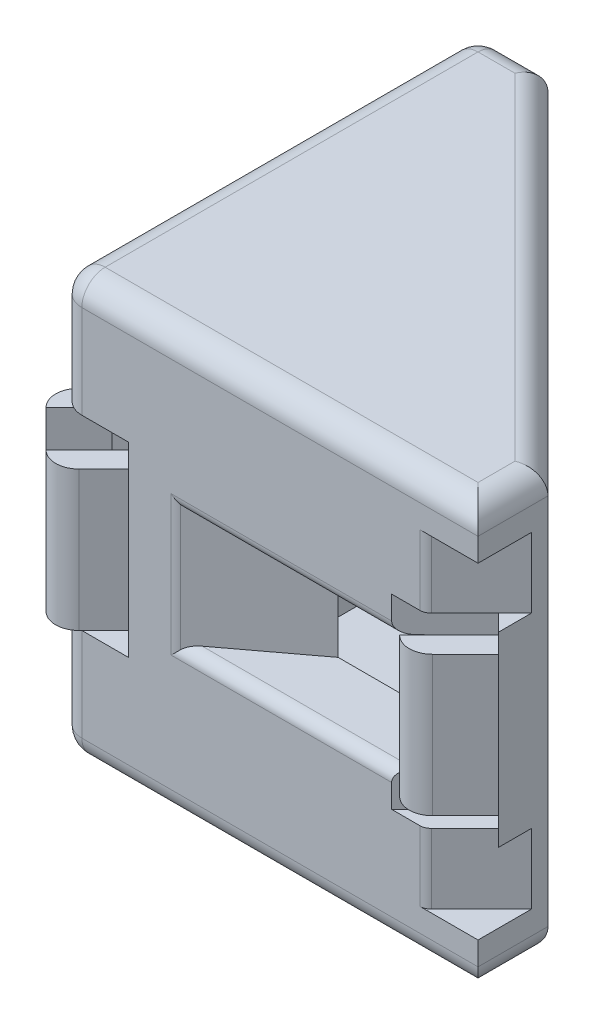
SolidWorks part; units mm, degrees
material "AISI Type A2 Tool Steel"
ref_plane "Front Plane" through (0, 0, 0) normal (0, 0, 1) x (1, 0, 0)
ref_plane "Top Plane" through (0, 0, 0) normal (0, 1, 0) x (1, 0, 0)
ref_plane "Right Plane" through (0, 0, 0) normal (1, 0, 0) x (0, 0, -1)
sketch "Sketch1" plane through (0, 0, 0) normal (0, 1, 0) x (1, 0, 0)
  line L0 (0, 0) -> (0, 18)
  line L1 (0, 18) -> (3, 18)
  line L2 (3, 18) -> (18, 3)
  line L3 (18, 3) -> (18, 0)
  line L4 (18, 0) -> (0, 0)
  dimension "D1" = 18
  dimension "D2" = 18
  dimension "D3" = 3
  dimension "D4" = 3
extrude "Boss-Extrude1" add sketch "Sketch1" along normal blind 18
sketch "Sketch2" plane through (0, 0, -18) normal (0, 0, -1) x (-1, 0, 0)
  line L0 (-18, 18) -> (-18, 0) construction
  line L1 (-18, 16) -> (-3, 16)
  line L2 (-18, 16) -> (-18, 2)
  line L3 (-18, 2) -> (-3, 2)
  line L4 (-3, 16) -> (-3, 2)
  line L5 (-3, 18) -> (-3, 0) construction
  line L6 (-18, 18) -> (-3, 18) construction
  line L7 (-18, 0) -> (-3, 0) construction
  dimension "D1" = 2
  dimension "D2" = 2
extrude "Cut-Extrude1" cut sketch "Sketch2" against normal up to vertex (15 mm away) up to point (18, 18, -3)
sketch "Sketch3" plane through (0, 0, -3) normal (0, 0, -1) x (-1, 0, 0)
  line L0 (-18, 16) -> (-18, 2) construction
  line L1 (-15, 11.5) -> (-9, 11.5)
  line L2 (-15, 11.5) -> (-15, 6.5)
  line L3 (-15, 6.5) -> (-9, 6.5)
  line L4 (-9, 11.5) -> (-9, 6.5)
  point P4 (-18, 9)
  point P7 (-15, 9)
  dimension "D1" = 6
  dimension "D2" = 5
  dimension "D3" = 3
sketch "Sketch4" plane through (3, 0, 0) normal (1, 0, 0) x (0, 0, -1)
  line L0 (9, 11.5) -> (15, 11.5)
  line L1 (9, 11.5) -> (9, 6.5)
  line L2 (9, 6.5) -> (15, 6.5)
  line L3 (15, 11.5) -> (15, 6.5)
  line L4 (18, 2) -> (18, 16) construction
  point P7 (18, 9)
  point P8 (15, 9)
  dimension "D1" = 3
  dimension "D2" = 6
  dimension "D3" = 5
sketch "Sketch5" plane through (0, 0, 0) normal (-1, 0, 0) x (0, 0, 1)
  line L1 (-15, 11.5) -> (-5, 11.5)
  line L2 (-15, 11.5) -> (-15, 6.5)
  line L3 (-15, 6.5) -> (-5, 6.5)
  line L4 (-5, 11.5) -> (-5, 6.5)
  dimension "D1" = 10
  dimension "D2" = 5
sketch "Sketch6" plane through (0, 0, 0) normal (0, 0, 1) x (1, 0, 0)
  line L1 (15, 11.5) -> (5, 11.5)
  line L2 (15, 11.5) -> (15, 6.5)
  line L3 (15, 6.5) -> (5, 6.5)
  line L4 (5, 11.5) -> (5, 6.5)
  dimension "D1" = 10
  dimension "D2" = 5
loft "Cut-Loft1" cut profiles "Sketch3", "Sketch6" connector at (9, 11.5, -3) connector at (5, 11.5, 0)
loft "Cut-Loft2" cut profiles "Sketch4", "Sketch5" connector at (3, 6.5, -9) connector at (0, 6.5, -5)
sketch "Sketch7" plane through (10.5, 0, -10.5) normal (0.7071, 0, -0.7071) x (-0.7071, 0, -0.7071)
  line L0 (10.6066, 2) -> (10.6066, 16) construction
  line L1 (11.1066, 16) -> (13.1066, 16)
  line L2 (11.1066, 16) -> (11.1066, 13)
  line L3 (11.1066, 13) -> (13.1066, 13)
  line L4 (13.1066, 16) -> (13.1066, 13)
  line L5 (11.1066, 5) -> (13.1066, 5)
  line L6 (11.1066, 5) -> (11.1066, 2)
  line L7 (11.1066, 2) -> (13.1066, 2)
  line L8 (13.1066, 5) -> (13.1066, 2)
  line L9 (-10.6066, 16) -> (10.6066, 16) construction
  line L10 (-13.1066, 16) -> (-11.1066, 16)
  line L11 (-13.1066, 16) -> (-13.1066, 13)
  line L12 (-13.1066, 13) -> (-11.1066, 13)
  line L13 (-11.1066, 16) -> (-11.1066, 13)
  line L14 (-13.1066, 5) -> (-11.1066, 5)
  line L15 (-13.1066, 5) -> (-13.1066, 2)
  line L16 (-13.1066, 2) -> (-11.1066, 2)
  line L17 (-11.1066, 5) -> (-11.1066, 2)
  line L18 (-10.6066, 16) -> (-10.6066, 2) construction
  line L19 (0, 16) -> (-10.6066, 16) construction
  point P10 (12.1066, 13)
  dimension "D1" = 2
  dimension "D2" = 2
  dimension "D3" = 0.5
  dimension "D4" = 0.5
  dimension "D5" = 3
  dimension "D6" = 3
  dimension "D7" = 8
  dimension "D8" = 8
  dimension "D9" = 2
  dimension "D10" = 3
  dimension "D11" = 0.5
extrude "Cut-Extrude2" cut sketch "Sketch7" against normal up to surface (1.7426 mm away) up to face at (0, 9, -9)
sketch "Sketch8" plane through (0, 5, 0) normal (0, -1, 0) x (1, 0, 0)
  line L5 (0.7072, -18) -> (2.2071, -16.5)
  line L6 (2.2929, -18) -> (0, -18) construction
  line L7 (0, -15.7071) -> (2.2929, -18) construction
  line L8 (2.2071, -16.5) -> (-0.114, -14.1789)
  line L9 (-0.114, -14.1789) -> (-1.614, -15.6789)
  line L10 (-1.614, -15.6789) -> (0.7072, -18)
  dimension "D1" = 1
extrude "Cut-Extrude4" cut sketch "Sketch8" against normal up to surface (8 mm away) body kept at (0, 0, 0) up to face at (0.7643, 13, -17.2357)
sketch "Sketch9" plane through (9.3536, 0, -9.3536) normal (-0.7071, 0, 0.7071) x (0.7071, 0, 0.7071)
  line L0 (-12.2279, 13) -> (-11.1066, 13) construction
  line L1 (-11.9779, 12) -> (-10.9779, 12)
  line L2 (-11.9779, 12) -> (-11.9779, 6)
  line L3 (-11.9779, 6) -> (-10.9779, 6)
  line L4 (-10.9779, 12) -> (-10.9779, 6)
  line L5 (-12.2279, 5) -> (-11.1066, 5) construction
  line L6 (-12.2279, 5) -> (-12.2279, 13) construction
  dimension "D1" = 1
  dimension "D2" = 1
  dimension "D3" = 0.25
  dimension "D4" = 1
extrude "Boss-Extrude2" add sketch "Sketch9" along normal blind 3
sketch "Sketch10" plane through (0, 13, 0) normal (0, 1, 0) x (1, 0, 0)
  line L0 (18.6478, 0.2309) -> (16.5858, 2.2929)
  line L2 (15.7071, 0) -> (18, 2.2929) construction
  line L3 (16.5858, 2.2929) -> (13.7144, -0.5785)
  line L4 (13.7144, -0.5785) -> (15.7764, -2.6405)
  line L5 (15.7764, -2.6405) -> (18.6478, 0.2309)
  dimension "D1" = 1
  dimension "D2" = 1
extrude "Cut-Extrude5" cut sketch "Sketch10" against normal up to surface (8 mm away) up to face at (17.2357, 5, -0.7643)
sketch "Sketch11" plane through (9.4393, 0, -9.4393) normal (-0.7071, 0, 0.7071) x (0.7071, 0, 0.7071)
  line L0 (12.1066, 13) -> (12.1066, 5) construction
  line L1 (11.8566, 12) -> (10.8566, 12)
  line L2 (11.8566, 12) -> (11.8566, 6)
  line L3 (11.8566, 6) -> (10.8566, 6)
  line L4 (10.8566, 12) -> (10.8566, 6)
  line L5 (11.1066, 13) -> (12.1066, 13) construction
  line L6 (11.1066, 5) -> (12.1066, 5) construction
  dimension "D1" = 1
  dimension "D2" = 0.25
  dimension "D3" = 1
  dimension "D4" = 1
extrude "Boss-Extrude3" add sketch "Sketch11" along normal blind 3
ref_plane "Plane1" through (0, 9, 0) normal (0, 1, 0) x (1, 0, 0)
sketch "Sketch12" plane through (0, 9, 0) normal (0, 1, 0) x (1, 0, 0)
  line L0 (0, 3) -> (0, 0)
  line L1 (0, 18) -> (0, 0) construction
  line L2 (0, 0) -> (3, 0)
  line L3 (0, 0) -> (18, 0) construction
  line L4 (3, 0) -> (0, 3)
  dimension "D1" = 3
  dimension "D2" = 3
extrude "Cut-Extrude6" cut sketch "Sketch12" against normal mid plane 8
sketch "Sketch13" plane through (1.5, 0, -1.5) normal (-0.7071, 0, 0.7071) x (0.7071, 0, 0.7071)
  line L0 (2.1213, 5) -> (2.1213, 13) construction
  line L1 (2.1213, 12) -> (1.1213, 12)
  line L2 (2.1213, 12) -> (2.1213, 6)
  line L3 (2.1213, 6) -> (1.1213, 6)
  line L4 (1.1213, 12) -> (1.1213, 6)
  line L5 (-2.1213, 5) -> (-2.1213, 13) construction
  line L6 (-2.1213, 12) -> (-1.1213, 12)
  line L7 (-2.1213, 12) -> (-2.1213, 6)
  line L8 (-2.1213, 6) -> (-1.1213, 6)
  line L9 (-1.1213, 12) -> (-1.1213, 6)
  line L10 (2.1213, 13) -> (-2.1213, 13) construction
  line L11 (2.1213, 5) -> (-2.1213, 5) construction
  dimension "D1" = 1
  dimension "D2" = 1
  dimension "D3" = 1
  dimension "D4" = 1
extrude "Boss-Extrude4" add sketch "Sketch13" along normal blind 2.5
sketch "Sketch14" plane through (1.5, 0, -1.5) normal (-0.7071, 0, 0.7071) x (0.7071, 0, 0.7071)
  line L0 (2.1213, 13) -> (-2.1213, 13) construction
  line L1 (-0.5, 13) -> (0.5, 13)
  line L2 (-0.5, 13) -> (-0.5, 5)
  line L3 (-0.5, 5) -> (0.5, 5)
  line L4 (0.5, 13) -> (0.5, 5)
  line L5 (2.1213, 5) -> (-2.1213, 5) construction
  point P8 (0, 13)
  dimension "D1" = 1
extrude "Boss-Extrude5" add sketch "Sketch14" along normal mid plane 1
fillet "Fillet3" radius 1 18 edges at (-1.2374, 9, -15.7019) (-1.7678, 9, -1.2322) (1.2322, 9, 1.7678) (15.7019, 9, 1.0659) (0, 1, -18) (0, 17, -18) (1.5, 18, -18) (1.5, 0, -18) (9, 0, 0) (18, 0, -1.5) (10.5, 0, -10.5) (9, 18, 0) (18, 18, -1.5) (10.5, 18, -10.5) (0, 18, -9) (0, 0, -9) (0, 15.5, 0) (0, 2.5, 0)
fillet "Fillet4" radius 0.5 10 edges at (15.7071, 3.5, 0) (15.7071, 14.5, 0) (0, 14.5, -15.7071) (0, 3.5, -15.7071)
